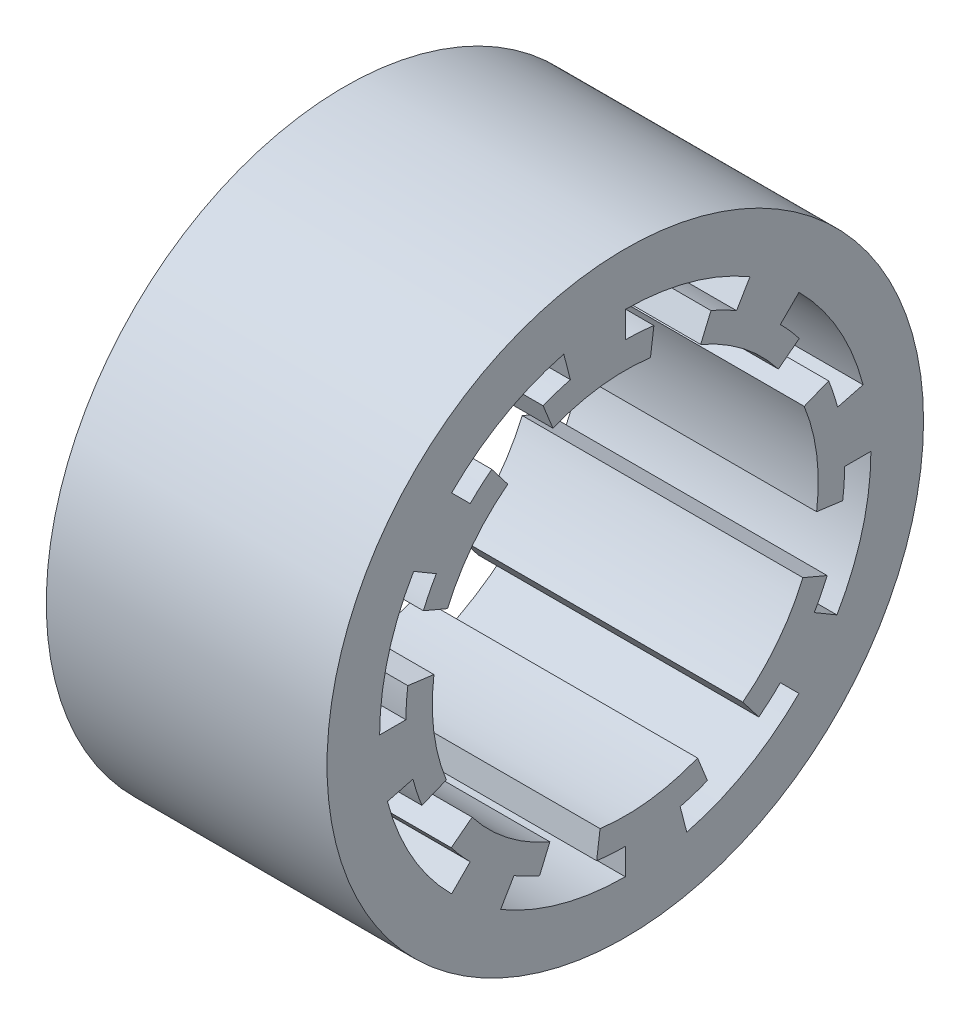
SolidWorks part; units mm, degrees
material "TPU 95A"
ref_plane "Front Plane" through (0, 0, 0) normal (1, 0, 0) x (0, 1, 0)
ref_plane "Top Plane" through (0, 0, 0) normal (0, 0, 1) x (0, 1, 0)
ref_plane "Right Plane" through (0, 0, 0) normal (0, 1, 0) x (-1, 0, 0)
sketch "Sketch1" plane through (0, 0, 0) normal (1, 0, 0) x (0, 1, 0)
  circle A0 centre (0, 0) radius 21.59
  circle A1 centre (0, 0) radius 17.78
  dimension "D1" = 43.18
  dimension "D2" = 35.56
extrude "Boss-Extrude1" add sketch "Sketch1" along normal blind 20.32
sketch "Sketch3" plane through (0, 0, 0) normal (1, 0, 0) x (0, 1, 0)
  line L0 (0, 0) -> (0, 17.78) construction
  line L1 (0, 0) -> (-4.4518, 17.2137) construction
  line L2 (0, 0) -> (-8.7553, 15.4749) construction
  line L3 (0, 0) -> (4.6018, 17.1742) construction
  line L4 (-4.4518, 17.2137) -> (-3.9748, 15.3693)
  line L5 (0, 0) -> (-5.9469, 14.719) construction
  line L6 (0, 0) -> (2.0721, 15.7392) construction
  line L7 (0, 17.78) -> (0, 15.875)
  line L8 (-5.9469, 14.719) -> (-5.2333, 12.9528)
  line L9 (2.0721, 15.7392) -> (1.8235, 13.8505)
  circle A0 centre (0, 0) radius 17.78 construction
  circle A1 centre (0, 0) radius 15.875 construction
  circle A3 centre (0, 0) radius 13.97 construction
  arc A4 (-3.9748, 15.3693) -> (-5.9469, 14.719) centre (0, 0) ccw
  arc A5 (0, 15.875) -> (2.0721, 15.7392) centre (0, 0) cw
  arc A6 (-5.2333, 12.9528) -> (1.8235, 13.8505) centre (0, 0) cw
  arc A7 (-4.4518, 17.2137) -> (0, 17.78) centre (0, 0) cw
  dimension "D6" = 35.56
  dimension "D7" = 31.75
  dimension "D8" = 27.94
  dimension "D1" = 14.5
  dimension "D2" = 15
  dimension "D3" = 15
  dimension "D4" = 7.5
  dimension "D5" = 7.5
extrude "Boss-Extrude2" add sketch "Sketch3" along normal up to surface (20.32 mm away) up to face at (20.32, 0, -21.59)
sketch "Sketch4" plane through (0, 0, 0) normal (0, 0, 1) x (0, 1, 0)
  line L0 (0, 0) -> (0, -7.3257) construction
  line L1 (21.59, 0) -> (-21.59, 0) construction
pattern_circular "CirPattern1" count 8 every 45 about axis through (0, 0, 0) along (1, 0, 0) of "Boss-Extrude2"
